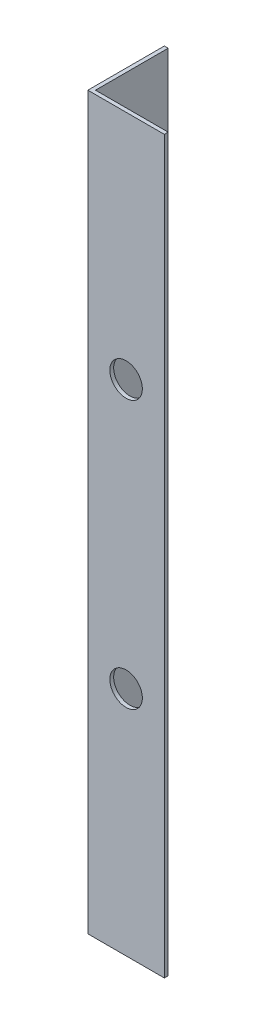
SolidWorks part; units mm, degrees
material "1060 Сплав"
ref_plane "Спереди" through (0, 0, 0) normal (0, 0, 1) x (1, 0, 0)
ref_plane "Сверху" through (0, 0, 0) normal (0, 1, 0) x (1, 0, 0)
ref_plane "Справа" through (0, 0, 0) normal (1, 0, 0) x (0, 0, -1)
sketch "Эскиз1" plane through (0, 0, 0) normal (0, 1, 0) x (1, 0, 0)
  line L0 (0, 0) -> (0, 20)
  line L1 (0, 20) -> (1, 20)
  line L2 (1, 20) -> (1, 1)
  line L3 (1, 1) -> (20, 1)
  line L4 (20, 1) -> (20, 0)
  line L5 (20, 0) -> (0, 0)
  dimension "D1" = 1
  dimension "D2" = 20
extrude "Бобышка-Вытянуть1" add sketch "Эскиз1" along normal blind 191
sketch "Эскиз2" plane through (0, 0, 0) normal (0, 0, 1) x (1, 0, 0)
  line L0 (10, 191) -> (10, 0) construction
  line L1 (0, 191) -> (20, 191) construction
  line L2 (0, 0) -> (20, 0) construction
  line L3 (0, 95.5) -> (20, 95.5) construction
  line L6 (0, 191) -> (0, 0) construction
  line L7 (20, 191) -> (20, 0) construction
  circle A1 centre (10, 130.5) radius 4.25
  circle A3 centre (10, 60.5) radius 4.25
  dimension "D1" = 70
  dimension "D2" = 35
  dimension "D4" = 8.5
extrude "Вырез-Вытянуть1" cut sketch "Эскиз2" against normal through all
